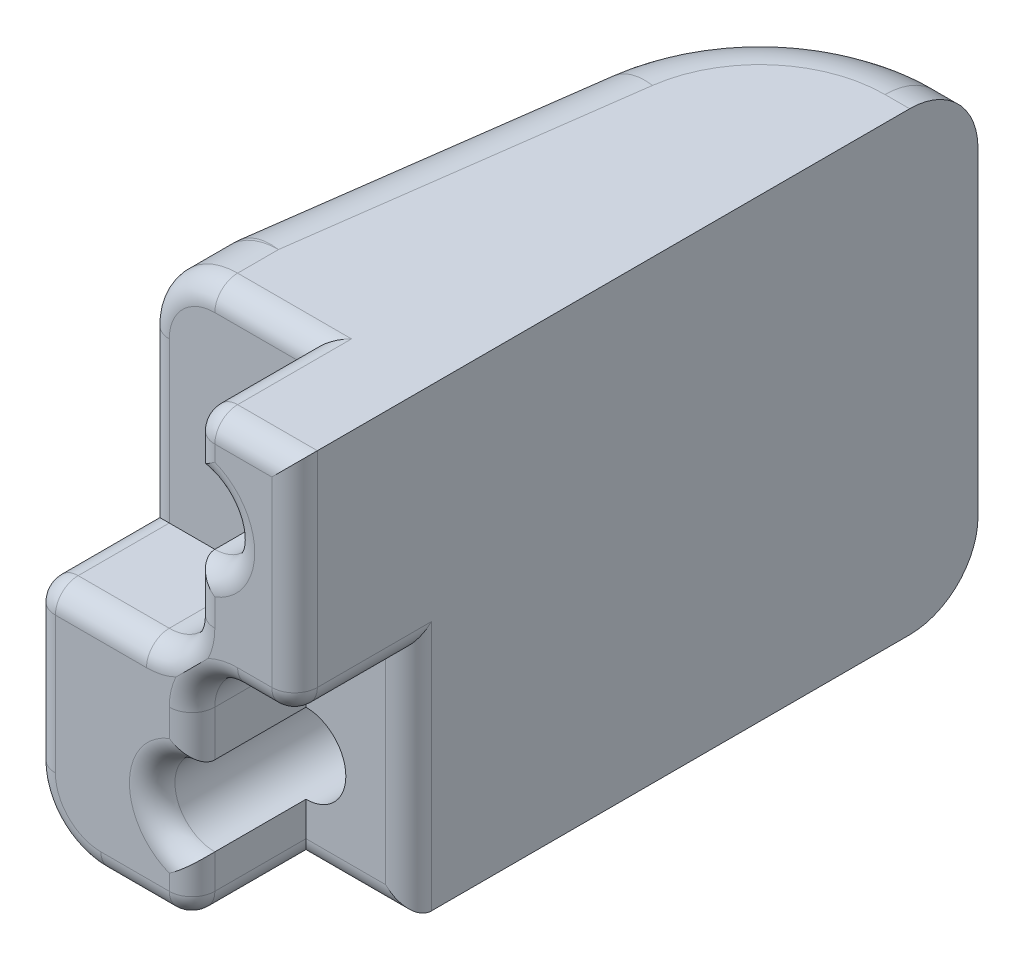
SolidWorks part; units mm, degrees
ref_plane "Front Plane" through (0, 0, 0) normal (0, 0, 1) x (1, 0, 0)
ref_plane "Top Plane" through (0, 0, 0) normal (0, 1, 0) x (1, 0, 0)
ref_plane "Right Plane" through (0, 0, 0) normal (1, 0, 0) x (0, 0, -1)
sketch "Sketch1" plane through (0, 0, 0) normal (0, 1, 0) x (1, 0, 0)
  line L1 (14, 0) -> (14, 8)
  line L2 (14, 8) -> (11, 30)
  line L3 (11, 30) -> (2.5, 30)
  line L4 (2.5, 30) -> (2.5, 8)
  line L8 (14, 8) -> (0, 8) construction
  line L9 (2.5, 8) -> (2.5, 0)
  line L10 (14, 0) -> (2.5, 0)
  line L11 (2.5, 0) -> (0, 0) construction
  line L12 (0, 0) -> (0, 8) construction
  dimension "D1" = 14
  dimension "D2" = 2.5
  dimension "D3" = 8
  dimension "D4" = 8.5
  dimension "D5" = 30
extrude "Boss-Extrude1" add sketch "Sketch1" along normal mid plane 20
sketch "Sketch2" plane through (0, 0, 0) normal (0, 0, 1) x (1, 0, 0)
  line L0 (0, 0) -> (7, 0) construction
  line L1 (14, 10) -> (7, 10)
  line L2 (14, 10) -> (14, 0)
  line L3 (14, 0) -> (9, 0)
  line L4 (7, 10) -> (7, 2)
  line L6 (5, 0) -> (2.5, 0)
  line L7 (7, -2) -> (7, -10)
  line L8 (7, -10) -> (2.5, -10)
  line L9 (2.5, 0) -> (2.5, -10)
  arc A0 (9, 0) -> (7, 2) centre (9, 2) cw
  arc A1 (5, 0) -> (7, -2) centre (5, -2) cw
  dimension "D2" = 2
  dimension "D3" = 2
  dimension "D1" = 7
extrude "Cut-Extrude1" cut sketch "Sketch2" against normal blind 5
sketch "Sketch3" plane through (0, 0, 0) normal (0, 0, 1) x (1, 0, 0)
  line L0 (0, 0) -> (14, 0) construction
  line L1 (7, -5.75) -> (7, 5.75) construction
  circle A0 centre (7, 5.75) radius 1.75
  circle A1 centre (7, -5.75) radius 1.75
  point P7 (7, 0)
  dimension "D1" = 11.5
  dimension "D2" = 3.5
extrude "Cut-Extrude2" cut sketch "Sketch3" against normal through all and the other way through all
sketch "Sketch4" plane through (0, 0, 0) normal (0, 0, 1) x (1, 0, 0)
  circle A0 centre (7, 5.75) radius 3.25
  circle A1 centre (7, -5.75) radius 3.25
  dimension "D1" = 6.5
extrude "Cut-Extrude3" cut sketch "Sketch4" against normal through all from offset 12 offset against normal yes
fillet "Fillet1" radius 8.5 1 edges at (11, 0, -30)
fillet "Fillet2" radius 1 22 edges at (7, -3, 0) (3.75, 0, 0) (7, 3, 0) (11.5, 0, 0) (10.5, -10, 0) (14, -5, 0) (8.75, -5.75, 0) (7, -8.75, 0) (2.5, 5, 0) (4.75, 10, 0) (7, 8.75, 0) (5.25, 5.75, 0) (6.4142, -0.5858, 0) (7.5858, 0.5858, 0) (2.5, 0, -2.5) (7, -10, -2.5) (7, 10, -2.5) (14, 0, -2.5) (2.5, -5, -5) (4.75, -10, -5) (10.5, 10, -5) (14, 5, -5)
fillet "Fillet3" radius 3 11 edges at (13.7071, -9.7071, -0.2929) (9.1701, 10, -27.9036) (13.0012, 10, -15.3242) (14, 10, -7) (14, -10, -4.5) (13.0012, -10, -15.3242) (9.1701, -10, -27.9036) (3.0402, 10, -30) (3.0402, -10, -30) (13.7071, 9.7071, -5.2929) (14, 0, -8)
mirror "Mirror4" about plane through (0, 0, 0) normal (1, 0, 0) of bodies 104
delete or keep bodies "Body-Delete/Keep 1" type delete bodies bodies 104
